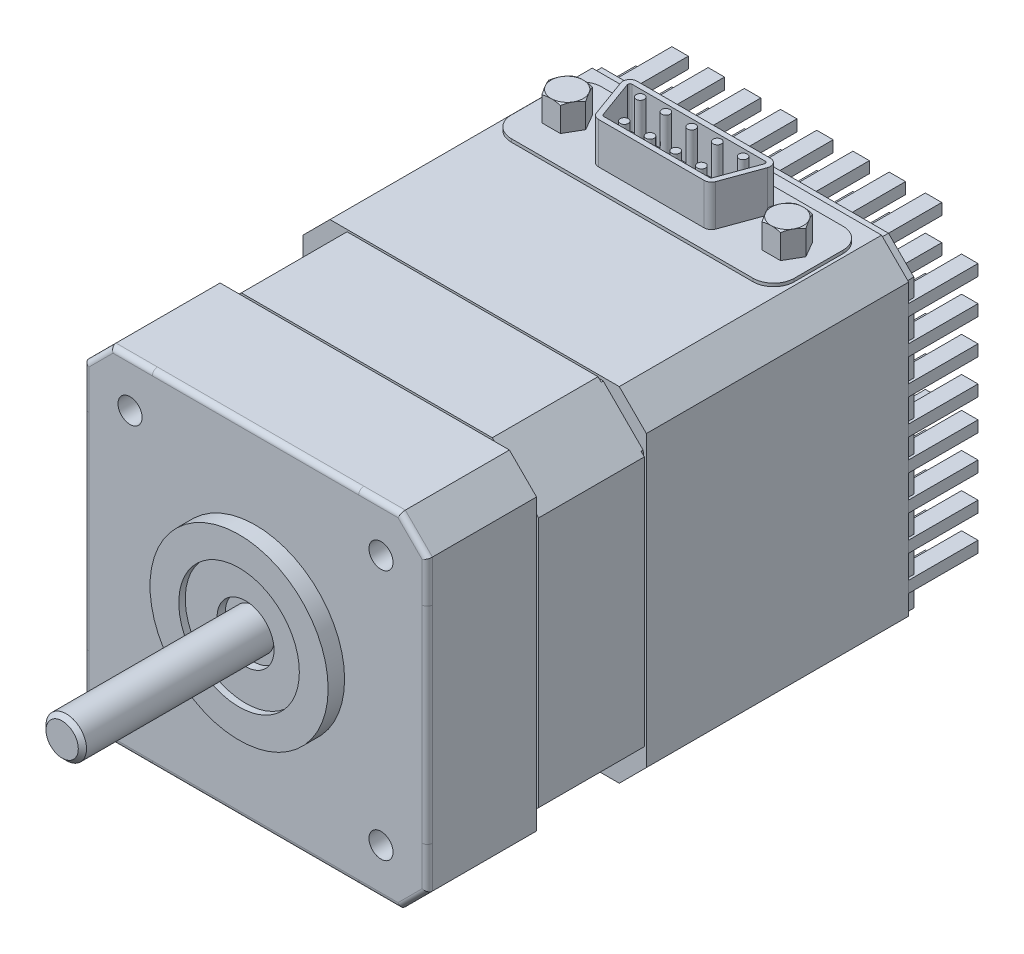
SolidWorks part; units mm, degrees
ref_plane "Front Plane" through (0, 0, 0) normal (0, 0, 1) x (1, 0, 0)
ref_plane "Top Plane" through (0, 0, 0) normal (0, 1, 0) x (1, 0, 0)
ref_plane "Right Plane" through (0, 0, 0) normal (1, 0, 0) x (0, 0, -1)
sketch "Sketch1" plane through (0, 0, 0) normal (0, 0, 1) x (1, 0, 0)
  line L0 (-21.209, -21.209) -> (21.209, 21.209) construction
  line L1 (-15.494, 21.209) -> (15.494, 21.209)
  line L2 (-21.209, 15.494) -> (-21.209, -15.494)
  line L3 (-15.494, -21.209) -> (15.494, -21.209)
  line L4 (21.209, 15.494) -> (21.209, -15.494)
  line L5 (0, 0) -> (0, 15.494) construction
  line L6 (-15.494, 15.494) -> (15.494, 15.494) construction
  line L7 (15.494, -15.494) -> (15.494, 15.494) construction
  line L8 (0, 0) -> (15.494, 0) construction
  circle A0 centre (-15.494, 15.494) radius 1.4859
  circle A1 centre (15.494, 15.494) radius 1.4859
  circle A2 centre (-15.494, -15.494) radius 1.4859
  circle A3 centre (15.494, -15.494) radius 1.4859
  arc A4 (15.494, 21.209) -> (21.209, 15.494) centre (15.494, 15.494) cw
  arc A5 (-15.494, 21.209) -> (-21.209, 15.494) centre (-15.494, 15.494) ccw
  arc A6 (-21.209, -15.494) -> (-15.494, -21.209) centre (-15.494, -15.494) ccw
  arc A7 (15.494, -21.209) -> (21.209, -15.494) centre (15.494, -15.494) ccw
  circle A8 centre (0, 0) radius 2.5019
  circle A9 centre (0, 0) radius 10.9982
  point P21 (-21.209, 21.209)
  dimension "H" = 2.9718
  dimension "A" = 5.0038
  dimension "Support Dia" = 21.9964
  dimension "E" = 42.418
  dimension "G" = 30.988
sketch "Sketch2" plane through (0, 0, 0) normal (0, 0, 1) x (1, 0, 0)
  line L0 (-15.494, 21.209) -> (15.494, 21.209) construction
  line L1 (21.209, 15.494) -> (21.209, -15.494) construction
  line L2 (-15.494, -21.209) -> (15.494, -21.209) construction
  line L3 (-21.209, 15.494) -> (-21.209, -15.494) construction
  line L4 (-15.494, 21.209) -> (15.494, 21.209)
  line L5 (21.209, 15.494) -> (21.209, -15.494)
  line L6 (-15.494, -21.209) -> (15.494, -21.209)
  line L7 (-21.209, 15.494) -> (-21.209, -15.494)
  arc A0 (21.209, 15.494) -> (15.494, 21.209) centre (15.494, 15.494) ccw construction
  arc A1 (15.494, -21.209) -> (21.209, -15.494) centre (15.494, -15.494) ccw construction
  arc A2 (-21.209, -15.494) -> (-15.494, -21.209) centre (-15.494, -15.494) ccw construction
  arc A3 (-15.494, 21.209) -> (-21.209, 15.494) centre (-15.494, 15.494) ccw construction
  arc A4 (21.209, 15.494) -> (15.494, 21.209) centre (15.494, 15.494) ccw
  arc A5 (15.494, -21.209) -> (21.209, -15.494) centre (15.494, -15.494) ccw
  arc A6 (-21.209, -15.494) -> (-15.494, -21.209) centre (-15.494, -15.494) ccw
  arc A7 (-15.494, 21.209) -> (-21.209, 15.494) centre (-15.494, 15.494) ccw
extrude "Extrude1" add sketch "Sketch2" against normal blind 68.072
ref_plane "Plane1" through (0, 0, -13.6144) normal (0, 0, 1) x (1, 0, 0)
ref_plane "Plane2" through (0, 0, -26.924) normal (0, 0, -1) x (-1, 0, 0)
sketch "Sketch3" plane through (0, 0, -13.6144) normal (0, 0, 1) x (1, 0, 0)
  line L4 (-21.209, 15.494) -> (-21.209, -15.494)
  line L5 (-15.494, -21.209) -> (15.494, -21.209)
  line L6 (21.209, -15.494) -> (21.209, 15.494)
  line L7 (15.494, 21.209) -> (-15.494, 21.209)
  line L8 (-21.209, 15.494) -> (-21.209, -15.494)
  line L9 (-15.494, -21.209) -> (15.494, -21.209)
  line L10 (21.209, -15.494) -> (21.209, 15.494)
  line L11 (15.494, 21.209) -> (-15.494, 21.209)
  arc A4 (-15.494, 21.209) -> (-21.209, 15.494) centre (-15.494, 15.494) ccw
  arc A5 (-21.209, -15.494) -> (-15.494, -21.209) centre (-15.494, -15.494) ccw
  arc A6 (15.494, -21.209) -> (21.209, -15.494) centre (15.494, -15.494) ccw
  arc A7 (21.209, 15.494) -> (15.494, 21.209) centre (15.494, 15.494) ccw
  arc A8 (-15.494, 21.209) -> (-21.209, 15.494) centre (-15.494, 15.494) ccw
  arc A9 (-21.209, -15.494) -> (-15.494, -21.209) centre (-15.494, -15.494) ccw
  arc A10 (15.494, -21.209) -> (21.209, -15.494) centre (15.494, -15.494) ccw
  arc A11 (21.209, 15.494) -> (15.494, 21.209) centre (15.494, 15.494) ccw
  dimension "D1" = 0
extrude "Cut-Extrude-Thin1" cut sketch "Sketch3" against normal mid plane 0.254 thin thin type mid plane wall 0.762
sketch "Sketch4" plane through (0, 0, -26.924) normal (0, 0, -1) x (-1, 0, 0)
  line L4 (21.209, -15.494) -> (21.209, 15.494)
  line L5 (-15.494, -21.209) -> (15.494, -21.209)
  line L6 (-21.209, 15.494) -> (-21.209, -15.494)
  line L7 (15.494, 21.209) -> (-15.494, 21.209)
  line L8 (21.209, -15.494) -> (21.209, 15.494)
  line L9 (-15.494, -21.209) -> (15.494, -21.209)
  line L10 (-21.209, 15.494) -> (-21.209, -15.494)
  line L11 (15.494, 21.209) -> (-15.494, 21.209)
  arc A4 (15.494, -21.209) -> (21.209, -15.494) centre (15.494, -15.494) ccw
  arc A5 (-21.209, -15.494) -> (-15.494, -21.209) centre (-15.494, -15.494) ccw
  arc A6 (-15.494, 21.209) -> (-21.209, 15.494) centre (-15.494, 15.494) ccw
  arc A7 (21.209, 15.494) -> (15.494, 21.209) centre (15.494, 15.494) ccw
  arc A8 (15.494, -21.209) -> (21.209, -15.494) centre (15.494, -15.494) ccw
  arc A9 (-21.209, -15.494) -> (-15.494, -21.209) centre (-15.494, -15.494) ccw
  arc A10 (-15.494, 21.209) -> (-21.209, 15.494) centre (-15.494, 15.494) ccw
  arc A11 (21.209, 15.494) -> (15.494, 21.209) centre (15.494, 15.494) ccw
  dimension "D1" = 0
extrude "Cut-Extrude-Thin2" cut sketch "Sketch4" against normal mid plane 0.254 thin thin type mid plane wall 0.762
sketch "Sketch5" plane through (0, 0, 0) normal (0, 0, 1) x (1, 0, 0)
  circle A0 centre (0, 0) radius 10.9982 construction
  circle A1 centre (0, 0) radius 10.9982
extrude "Extrude2" add sketch "Sketch5" along normal blind 2.032
sketch "Sketch6" plane through (0, 0, 0) normal (0, 0, 1) x (1, 0, 0)
  circle A0 centre (0, 0) radius 2.5019 construction
  circle A1 centre (0, 0) radius 2.5019
extrude "Extrude3" add sketch "Sketch6" along normal blind 23.876
chamfer "Chamfer1" distance 0.508 angle 45 1 edges at (2.5019, 0, 23.876)
sketch "Sketch7" plane through (0, 0, 0) normal (0, 0, 1) x (1, 0, 0)
  circle A0 centre (15.494, 15.494) radius 1.4859 construction
  circle A1 centre (15.494, -15.494) radius 1.4859 construction
  circle A2 centre (-15.494, -15.494) radius 1.4859 construction
  circle A3 centre (-15.494, 15.494) radius 1.4859 construction
  circle A4 centre (15.494, 15.494) radius 1.4859
  circle A5 centre (15.494, -15.494) radius 1.4859
  circle A6 centre (-15.494, -15.494) radius 1.4859
  circle A7 centre (-15.494, 15.494) radius 1.4859
extrude "Cut-Extrude1" cut sketch "Sketch7" against normal blind 3.9624
sketch "Sketch9" plane through (0, 0, 2.032) normal (0, 0, 1) x (1, 0, 0)
  circle A0 centre (0, 0) radius 2.5019 construction
  circle A1 centre (0, 0) radius 2.5019
  circle A4 centre (0, 0) radius 7.4422
  circle A5 centre (0, 0) radius 7.4422
  dimension "D1" = 3.556
extrude "Cut-Extrude3" cut sketch "Sketch9" against normal blind 0.8001
sketch "Sketch8" plane through (0, 0, 1.2319) normal (0, 0, 1) x (1, 0, 0)
  circle A0 centre (0, 0) radius 2.5019 construction
  circle A1 centre (0, 0) radius 2.5019
  circle A2 centre (0, 0) radius 3.5179
  dimension "D1" = 1.016
extrude "Cut-Extrude2" cut sketch "Sketch8" against normal blind 1.016
sketch "Sketch10" plane through (0, 0, -68.072) normal (0, 0, -1) x (-1, 0, 0)
  line L0 (9.779, 15.494) -> (9.779, 21.209)
  line L1 (15.494, 9.779) -> (21.209, 9.779)
  line L2 (-9.779, 15.494) -> (-9.779, 21.209)
  line L3 (-15.494, 9.779) -> (-21.209, 9.779)
  line L4 (-21.209, -9.779) -> (-15.494, -9.779)
  line L5 (-9.779, -15.494) -> (-9.779, -21.209)
  line L6 (9.779, -15.494) -> (9.779, -21.209)
  line L7 (15.494, -9.779) -> (21.209, -9.779)
  line L8 (-21.209, 15.494) -> (-21.209, -15.494) construction
  line L9 (-21.209, 21.209) -> (-9.779, 21.209)
  line L10 (-21.209, 21.209) -> (-21.209, 9.779)
  line L11 (-21.209, -21.209) -> (-9.779, -21.209)
  line L12 (21.209, 21.209) -> (21.209, 9.779)
  line L13 (15.494, -21.209) -> (-15.494, -21.209) construction
  line L14 (15.494, 21.209) -> (-15.494, 21.209) construction
  line L15 (21.209, 15.494) -> (21.209, -15.494) construction
  line L16 (21.209, -9.779) -> (21.209, -21.209)
  line L17 (9.779, 21.209) -> (21.209, 21.209)
  line L18 (-21.209, -9.779) -> (-21.209, -21.209)
  line L19 (9.779, -21.209) -> (21.209, -21.209)
  arc A0 (-15.494, 9.779) -> (-9.779, 15.494) centre (-15.494, 15.494) ccw
  arc A1 (9.779, 15.494) -> (15.494, 9.779) centre (15.494, 15.494) ccw
  arc A2 (15.494, -9.779) -> (9.779, -15.494) centre (15.494, -15.494) ccw
  arc A3 (-9.779, -15.494) -> (-15.494, -9.779) centre (-15.494, -15.494) ccw
  arc A4 (-21.209, -15.494) -> (-15.494, -21.209) centre (-15.494, -15.494) ccw construction
  circle A5 centre (-15.494, 15.494) radius 1.4859 construction
  circle A6 centre (15.494, 15.494) radius 1.4859 construction
  circle A7 centre (15.494, -15.494) radius 1.4859 construction
extrude "Cut-Extrude4" cut sketch "Sketch10" against normal blind 7.9375
fillet "Fillet1" radius 1.016 8 edges at (-21.209, -9.779, -64.1033) (-9.779, -21.209, -64.1033) (21.209, -9.779, -64.1033) (9.779, -21.209, -64.1033) (-21.209, 9.779, -64.1033) (-9.779, 21.209, -64.1033) (9.779, 21.209, -64.1033) (21.209, 9.779, -64.1033)
fillet "Fillet2" radius 0.635 44 edges at (-21.209, -12.1285, -60.1345) (-19.5351, -19.5351, -60.1345) (12.1285, -21.209, -60.1345) (21.209, -12.1285, -60.1345) (12.1285, 21.209, -60.1345) (19.5351, 19.5351, -60.1345) (19.5351, 19.5351, 0) (21.209, 0, 0) (19.5351, -19.5351, 0) (0, -21.209, 0) (-19.5351, -19.5351, 0) (-21.209, 0, 0) (-19.5351, 19.5351, 0) (-12.1285, 21.209, -60.1345) (-21.209, 12.1285, -60.1345) (-9.779, 17.8435, -68.072) (-11.4529, 11.4529, -68.072) (-17.8435, 9.779, -68.072) (-20.9114, 9.4814, -68.072) (-21.209, 0, -68.072) (-20.9114, -9.4814, -68.072) (-17.8435, -9.779, -68.072) (-11.4529, -11.4529, -68.072) (-9.779, -17.8435, -68.072) (-9.4814, -20.9114, -68.072) (0, -21.209, -68.072) (9.4814, -20.9114, -68.072) (9.779, -17.8435, -68.072) (11.4529, -11.4529, -68.072) (17.8435, -9.779, -68.072) (20.9114, -9.4814, -68.072) (21.209, 0, -68.072) (20.9114, 9.4814, -68.072) (17.8435, 9.779, -68.072) (11.4529, 11.4529, -68.072) (9.779, 17.8435, -68.072) (9.4814, 20.9114, -68.072) (0, 21.209, -68.072) (-12.1285, -21.209, -60.1345) (19.5351, -19.5351, -60.1345) (21.209, 12.1285, -60.1345) (0, 21.209, 0) (-19.5351, 19.5351, -60.1345) (-9.4814, 20.9114, -68.072)
sketch "Sketch11" plane through (0, 0, -60.1345) normal (0, 0, -1) x (-1, 0, 0)
  circle A0 centre (15.494, 15.494) radius 1.4859 construction
  circle A1 centre (-15.494, 15.494) radius 5.08
  arc A2 (20.574, 15.494) -> (15.494, 20.574) centre (15.494, 15.494) ccw construction
  circle A3 centre (15.494, 15.494) radius 5.08
  circle A4 centre (15.494, -15.494) radius 5.08
  circle A5 centre (-15.494, -15.494) radius 5.08
  circle A6 centre (-15.494, 15.494) radius 1.4859 construction
  circle A7 centre (-15.494, -15.494) radius 1.4859 construction
  circle A8 centre (15.494, -15.494) radius 1.4859 construction
  arc A10 (12.0703, 11.7415) -> (12.0472, 11.7644) centre (12.6853, 12.3834) ccw construction
extrude "Extrude4" add sketch "Sketch11" along normal blind 0.508
dome "Dome1" faces to dome 1 distance 3.9688 reverse direction no elliptical dome yes face at (10.414, -15.494, -60.6425) parameters "D1"=3.9688
dome "Dome2" faces to dome 1 distance 3.9688 reverse direction no elliptical dome yes face at (-20.574, -15.494, -60.6425) parameters "D1"=3.9688
dome "Dome3" faces to dome 1 distance 3.9688 reverse direction no elliptical dome yes face at (10.414, 15.494, -60.6425) parameters "D1"=3.9688
dome "Dome4" faces to dome 1 distance 3.9688 reverse direction no elliptical dome yes face at (-20.574, 15.494, -60.6425) parameters "D1"=3.9688
sketch "Sketch12" [suppressed] plane through (0, 14.097, 0) normal (0, 1, 0) x (-1, 0, 0)
  line L0 (0, 0) -> (0, -22.987) construction
  line L1 (-8.001, -32.004) -> (8.001, -32.004)
  line L2 (-8.001, -32.004) -> (-8.001, -22.987)
  line L3 (-8.001, -22.987) -> (8.001, -22.987)
  line L4 (8.001, -32.004) -> (8.001, -22.987)
  line L5 (8.001, -32.004) -> (-8.001, -32.004) construction
  line L6 (-8.001, -29.083) -> (-8.001, -31.369) construction
  line L7 (-11.557, -22.987) -> (11.557, -22.987) construction
extrude "Extrude5" [suppressed] add sketch "Sketch12" along normal blind 2.3749 and the other way up to next
chamfer "Chamfer2" [suppressed] distance 2.286 distance2 0.762
fillet "Fillet3" [suppressed] radius 0.508
sketch "Sketch13" [suppressed] plane through (0, 0, -32.004) normal (0, 0, -1) x (-1, 0, 0)
  line L1 (-7.493, 13.589) -> (7.493, 13.589)
  line L7 (-7.493, 16.4719) -> (7.493, 16.4719) construction
  line L8 (8.001, 13.462) -> (8.001, 15.9639) construction
  line L9 (-8.001, 13.462) -> (-8.001, 15.9639) construction
  line L13 (7.493, 15.9639) -> (7.493, 13.589)
  line L14 (-7.493, 15.9639) -> (7.493, 15.9639)
  line L15 (-7.493, 13.589) -> (-7.493, 15.9639)
  dimension "D1" = 0.508
  dimension "D2" = 0.508
  dimension "D3" = 0.508
  dimension "D4" = 2.3749
extrude "Cut-Extrude5" [suppressed] cut sketch "Sketch13" against normal blind 3.175
fillet "Fillet4" [suppressed] radius 0.254
sketch "Sketch14" [suppressed] plane through (0, 0, -28.829) normal (0, 0, -1) x (-1, 0, 0)
  line L4 (7.493, 13.589) -> (7.493, 15.9639)
  line L5 (7.493, 15.9639) -> (-7.493, 15.9639)
  line L6 (-7.493, 15.9639) -> (-7.493, 13.589)
  line L7 (-7.493, 13.589) -> (7.493, 13.589)
  line L8 (7.493, 13.589) -> (7.493, 15.9639)
  line L9 (7.493, 15.9639) -> (-7.493, 15.9639)
  line L10 (-7.493, 15.9639) -> (-7.493, 13.589)
  line L11 (-7.493, 13.589) -> (7.493, 13.589)
  dimension "D1" = 0
extrude "Extrude6" [suppressed] add sketch "Sketch14" along normal blind 3.9624
sketch "Sketch15" [suppressed] plane through (0, 0, -32.7914) normal (0, 0, -1) x (-1, 0, 0)
  line L8 (-7.874, 13.208) -> (7.874, 13.208)
  line L9 (7.874, 13.208) -> (7.874, 16.3449)
  line L10 (7.874, 16.3449) -> (-7.874, 16.3449)
  line L11 (-7.874, 16.3449) -> (-7.874, 13.208)
  line L12 (-7.874, 13.208) -> (7.874, 13.208)
  line L13 (7.874, 13.208) -> (7.874, 16.3449)
  line L14 (7.874, 16.3449) -> (-7.874, 16.3449)
  line L15 (-7.874, 16.3449) -> (-7.874, 13.208)
  dimension "D1" = 0.381
extrude "Extrude7" [suppressed] add sketch "Sketch15" along normal blind 0.381
fillet "Fillet5" [suppressed] radius 0.762
sketch "Sketch16" [suppressed] plane through (0, 17.653, 0) normal (0, 1, 0) x (-1, 0, 0)
  line L0 (12.954, -14.7139) -> (-12.954, -14.7139) construction
  line L1 (-6.477, -14.7139) -> (6.477, -14.7139)
  line L2 (-6.477, -14.7139) -> (-6.477, -19.4764)
  line L3 (-6.477, -19.4764) -> (6.477, -19.4764)
  line L4 (6.477, -14.7139) -> (6.477, -19.4764)
  line L5 (7.239, -33.401) -> (7.239, -31.877) construction
  point P6 (7.239, -32.639)
  dimension "D1" = 0.762
  dimension "D2" = 0.762
  dimension "D3" = 4.7625
extrude "Extrude8" [suppressed] add sketch "Sketch16" along normal blind 1.397
fillet "Fillet6" [suppressed] radius 0.889
sketch "Sketch17" [suppressed] plane through (0, 19.05, 0) normal (0, 1, 0) x (-1, 0, 0)
  line L8 (5.588, -15.2219) -> (-5.588, -15.2219)
  line L9 (-5.969, -15.6029) -> (-5.969, -18.5874)
  line L10 (-5.588, -18.9684) -> (5.588, -18.9684)
  line L11 (5.969, -18.5874) -> (5.969, -15.6029)
  line L12 (5.588, -15.2219) -> (-5.588, -15.2219)
  line L13 (-5.969, -15.6029) -> (-5.969, -18.5874)
  line L14 (-5.588, -18.9684) -> (5.588, -18.9684)
  line L15 (5.969, -18.5874) -> (5.969, -15.6029)
  arc A8 (-5.588, -15.2219) -> (-5.969, -15.6029) centre (-5.588, -15.6029) ccw
  arc A9 (-5.969, -18.5874) -> (-5.588, -18.9684) centre (-5.588, -18.5874) ccw
  arc A10 (5.588, -18.9684) -> (5.969, -18.5874) centre (5.588, -18.5874) ccw
  arc A11 (5.969, -15.6029) -> (5.588, -15.2219) centre (5.588, -15.6029) ccw
  arc A12 (-5.588, -15.2219) -> (-5.969, -15.6029) centre (-5.588, -15.6029) ccw
  arc A13 (-5.969, -18.5874) -> (-5.588, -18.9684) centre (-5.588, -18.5874) ccw
  arc A14 (5.588, -18.9684) -> (5.969, -18.5874) centre (5.588, -18.5874) ccw
  arc A15 (5.969, -15.6029) -> (5.588, -15.2219) centre (5.588, -15.6029) ccw
  dimension "D1" = 0.508
extrude "Cut-Extrude6" [suppressed] cut sketch "Sketch17" against normal blind 0.127
sketch "Sketch18" plane through (0, 0, 0) normal (0, 0, 1) x (1, 0, 0)
  line L0 (-21.209, 17.8612) -> (-17.8612, 21.209)
  line L1 (0, 0) -> (0, 16.0858) construction
  line L2 (-15.494, 21.209) -> (15.494, 21.209) construction
  line L3 (-21.209, -15.494) -> (-21.209, 15.494) construction
  line L4 (-17.8612, 21.209) -> (-12.7381, 21.209)
  line L5 (-21.209, 12.7381) -> (-21.209, 17.8612)
  line L6 (-21.209, 12.7381) -> (-15.494, 12.7381)
  line L7 (-12.7381, 15.494) -> (-12.7381, 21.209)
  line L8 (12.7381, 15.494) -> (12.7381, 21.209)
  line L9 (21.209, 12.7381) -> (15.494, 12.7381)
  line L10 (21.209, 12.7381) -> (21.209, 17.8612)
  line L11 (17.8612, 21.209) -> (12.7381, 21.209)
  line L12 (21.209, 17.8612) -> (17.8612, 21.209)
  line L13 (0, 0) -> (14.0244, 0) construction
  line L14 (21.209, -17.8612) -> (17.8612, -21.209)
  line L15 (17.8612, -21.209) -> (12.7381, -21.209)
  line L16 (21.209, -12.7381) -> (21.209, -17.8612)
  line L17 (21.209, -12.7381) -> (15.494, -12.7381)
  line L18 (12.7381, -15.494) -> (12.7381, -21.209)
  line L19 (-12.7381, -15.494) -> (-12.7381, -21.209)
  line L20 (-21.209, -12.7381) -> (-15.494, -12.7381)
  line L21 (-21.209, -12.7381) -> (-21.209, -17.8612)
  line L22 (-17.8612, -21.209) -> (-12.7381, -21.209)
  line L23 (-21.209, -17.8612) -> (-17.8612, -21.209)
  arc A0 (12.7381, 15.494) -> (15.494, 12.7381) centre (15.494, 15.494) cw
  arc A1 (-15.494, 21.209) -> (-21.209, 15.494) centre (-15.494, 15.494) ccw construction
  arc A2 (-12.7381, -15.494) -> (-15.494, -12.7381) centre (-15.494, -15.494) cw
  arc A3 (12.7381, -15.494) -> (15.494, -12.7381) centre (15.494, -15.494) ccw
  circle A4 centre (-15.494, 15.494) radius 2.7559
  arc A5 (-12.7381, 15.494) -> (-15.494, 12.7381) centre (-15.494, 15.494) ccw
  dimension "D1" = 45
  dimension "D2" = 1.27
extrude "Extrude9" add sketch "Sketch18" against normal up to surface (13.4874 mm away) up to face at (0, 0, -13.4874)
fillet "Fillet7" radius 0.635 12 edges at (-21.209, -15.2997, 0) (-19.5351, -19.5351, 0) (-15.2997, -21.209, 0) (15.2997, -21.209, 0) (19.5351, -19.5351, 0) (21.209, -15.2997, 0) (21.209, 15.2997, 0) (19.5351, 19.5351, 0) (15.2997, 21.209, 0) (-15.2997, 21.209, 0) (-19.5351, 19.5351, 0) (-21.209, 15.2997, 0)
sketch "Sketch19" plane through (0, 0, -27.051) normal (0, 0, 1) x (1, 0, 0)
  line L5 (12.7381, 21.209) -> (12.7381, 15.494)
  line L6 (15.494, 12.7381) -> (21.209, 12.7381)
  line L7 (21.209, 12.7381) -> (21.209, 17.8612)
  line L8 (21.209, 17.8612) -> (17.8612, 21.209)
  line L9 (17.8612, 21.209) -> (12.7381, 21.209)
  line L10 (12.7381, 21.209) -> (12.7381, 15.494)
  line L11 (15.494, 12.7381) -> (21.209, 12.7381)
  line L12 (21.209, 12.7381) -> (21.209, 17.8612)
  line L13 (21.209, 17.8612) -> (17.8612, 21.209)
  line L14 (17.8612, 21.209) -> (12.7381, 21.209)
  line L15 (-21.209, 12.7381) -> (-15.494, 12.7381)
  line L16 (-21.209, 17.8612) -> (-21.209, 12.7381)
  line L17 (-17.8612, 21.209) -> (-21.209, 17.8612)
  line L18 (-12.7381, 21.209) -> (-17.8612, 21.209)
  line L19 (-12.7381, 15.494) -> (-12.7381, 21.209)
  line L20 (-21.209, 12.7381) -> (-15.494, 12.7381)
  line L21 (-21.209, 17.8612) -> (-21.209, 12.7381)
  line L22 (-17.8612, 21.209) -> (-21.209, 17.8612)
  line L23 (-12.7381, 21.209) -> (-17.8612, 21.209)
  line L24 (-12.7381, 15.494) -> (-12.7381, 21.209)
  line L25 (-12.7381, -21.209) -> (-12.7381, -15.494)
  line L26 (-15.494, -12.7381) -> (-21.209, -12.7381)
  line L27 (-21.209, -12.7381) -> (-21.209, -17.8612)
  line L28 (-21.209, -17.8612) -> (-17.8612, -21.209)
  line L29 (-17.8612, -21.209) -> (-12.7381, -21.209)
  line L30 (-12.7381, -21.209) -> (-12.7381, -15.494)
  line L31 (-15.494, -12.7381) -> (-21.209, -12.7381)
  line L32 (-21.209, -12.7381) -> (-21.209, -17.8612)
  line L33 (-21.209, -17.8612) -> (-17.8612, -21.209)
  line L34 (-17.8612, -21.209) -> (-12.7381, -21.209)
  line L35 (17.8612, -21.209) -> (21.209, -17.8612)
  line L36 (12.7381, -21.209) -> (17.8612, -21.209)
  line L37 (12.7381, -15.494) -> (12.7381, -21.209)
  line L38 (21.209, -12.7381) -> (15.494, -12.7381)
  line L39 (21.209, -17.8612) -> (21.209, -12.7381)
  line L40 (17.8612, -21.209) -> (21.209, -17.8612)
  line L41 (12.7381, -21.209) -> (17.8612, -21.209)
  line L42 (12.7381, -15.494) -> (12.7381, -21.209)
  line L43 (21.209, -12.7381) -> (15.494, -12.7381)
  line L44 (21.209, -17.8612) -> (21.209, -12.7381)
  arc A1 (15.494, 12.7381) -> (12.7381, 15.494) centre (15.494, 15.494) ccw
  arc A2 (15.494, 12.7381) -> (12.7381, 15.494) centre (15.494, 15.494) ccw
  arc A3 (-12.7381, 15.494) -> (-15.494, 12.7381) centre (-15.494, 15.494) ccw
  arc A4 (-12.7381, 15.494) -> (-15.494, 12.7381) centre (-15.494, 15.494) ccw
  arc A5 (-15.494, -12.7381) -> (-12.7381, -15.494) centre (-15.494, -15.494) ccw
  arc A6 (-15.494, -12.7381) -> (-12.7381, -15.494) centre (-15.494, -15.494) ccw
  arc A7 (12.7381, -15.494) -> (15.494, -12.7381) centre (15.494, -15.494) ccw
  arc A8 (12.7381, -15.494) -> (15.494, -12.7381) centre (15.494, -15.494) ccw
  dimension "D1" = 0
  dimension "D2" = 0
  dimension "D3" = 0
  dimension "D4" = 0
extrude "Extrude10" add sketch "Sketch19" against normal up to surface (33.0835 mm away) up to face at (14.2873, 14.2873, -60.1345)
sketch "Sketch21" plane through (0, 21.209, 0) normal (0, 1, 0) x (-1, 0, 0)
  line L0 (-17.4625, -52.07) -> (0, -52.07) construction
  line L1 (-17.4625, -57.6263) -> (17.4625, -57.6262)
  line L2 (-17.4625, -57.6263) -> (-17.4625, -46.5138)
  line L3 (-17.4625, -46.5138) -> (17.4625, -46.5138)
  line L4 (17.4625, -57.6262) -> (17.4625, -46.5138)
  line L5 (8.763, -68.072) -> (-8.763, -68.072) construction
  line L6 (0, 0) -> (0, -52.07) construction
  line L7 (-13.589, -61.8191) -> (-13.589, -41.9159) construction
  line L8 (-21.209, -60.1345) -> (-21.209, -27.051) construction
  line L9 (6.35, -53.848) -> (-6.2857, -53.848) construction
  line L10 (0, -52.07) -> (0, -57.6262) construction
  line L11 (14.7328, -54.0512) -> (12.4452, -54.0512)
  line L12 (-11.3013, -52.07) -> (-12.4452, -50.0888)
  line L13 (-12.4452, -50.0888) -> (-14.7328, -50.0888)
  line L14 (-14.7328, -50.0888) -> (-15.8767, -52.07)
  line L15 (-15.8767, -52.07) -> (-14.7328, -54.0512)
  line L16 (-14.7328, -54.0512) -> (-12.4452, -54.0512)
  line L17 (-12.4452, -54.0512) -> (-11.3013, -52.07)
  line L18 (15.8767, -52.07) -> (14.7328, -54.0512)
  line L19 (14.7328, -50.0888) -> (15.8767, -52.07)
  line L20 (12.4452, -50.0888) -> (14.7328, -50.0888)
  line L21 (11.3013, -52.07) -> (12.4452, -50.0888)
  line L22 (12.4452, -54.0512) -> (11.3013, -52.07)
  line L23 (-9.4966, -55.3402) -> (9.4966, -55.3402)
  line L24 (9.4966, -55.3402) -> (7.1438, -48.876)
  line L25 (7.1438, -48.876) -> (-7.1437, -48.876)
  line L26 (-7.1437, -48.876) -> (-9.4966, -55.3402)
  line L27 (6.3103, -50.292) -> (-6.2857, -50.292) construction
  line L28 (-6.2857, -50.292) -> (-6.2857, -52.07) construction
  line L29 (-6.2857, -53.848) -> (-6.2857, -52.07) construction
  circle A0 centre (-13.589, -52.07) radius 1.9812 construction
  circle A1 centre (0, -53.848) radius 0.508
  circle A2 centre (1.5875, -50.292) radius 0.508
  circle A3 centre (4.7625, -50.292) radius 0.508
  circle A4 centre (6.35, -53.848) radius 0.508
  circle A5 centre (3.175, -53.848) radius 0.508
  circle A6 centre (-3.175, -53.848) radius 0.508
  circle A7 centre (-6.35, -53.848) radius 0.508
  circle A8 centre (-4.7625, -50.292) radius 0.508
  circle A9 centre (-1.5875, -50.292) radius 0.508
  dimension "D4" = 3.9624
  dimension "D13" = 1.016
  dimension "D1" = 16.002
  dimension "D2" = 7.62
  dimension "D3" = 2.286
  dimension "D5" = 17.4625
  dimension "D6" = 11.1125
  dimension "D7" = 2.3622
  dimension "D8" = 20
  dimension "D9" = 14.2875
  dimension "D10" = 7.1437
  dimension "D11" = 1.778
  dimension "D12" = 1.5875
  dimension "D14" = 3.175
  dimension "D15" = 3.175
  dimension "D16" = 3.175
sketch "Sketch22" plane through (0, 0, -13.7414) normal (0, 0, 1) x (1, 0, 0)
  line L0 (15.494, 21.209) -> (21.209, 15.494)
  line L1 (21.209, 15.494) -> (21.209, 21.209)
  line L2 (21.209, 21.209) -> (15.494, 21.209)
  line L3 (0, 0) -> (0, 24.2976) construction
  line L4 (-21.209, 21.209) -> (-15.494, 21.209)
  line L5 (-21.209, 15.494) -> (-21.209, 21.209)
  line L6 (-15.494, 21.209) -> (-21.209, 15.494)
  line L7 (0, 0) -> (18.2844, 0) construction
  line L8 (-15.494, -21.209) -> (-21.209, -15.494)
  line L9 (-21.209, -15.494) -> (-21.209, -21.209)
  line L10 (-21.209, -21.209) -> (-15.494, -21.209)
  line L11 (21.209, -21.209) -> (15.494, -21.209)
  line L12 (21.209, -15.494) -> (21.209, -21.209)
  line L13 (15.494, -21.209) -> (21.209, -15.494)
extrude "Cut-Extrude7" cut sketch "Sketch22" against normal up to surface (13.3096 mm away) up to face at (0, 0, -27.051)
sketch "Sketch23" plane through (0, 0, -68.072) normal (0, 0, -1) x (-1, 0, 0)
  circle A0 centre (-15.494, 15.494) radius 5.08 construction
  circle A1 centre (-15.494, 15.494) radius 5.08
  circle A2 centre (15.494, 15.494) radius 5.08 construction
  circle A3 centre (15.494, 15.494) radius 5.08
  circle A4 centre (15.494, -15.494) radius 5.08 construction
  circle A5 centre (15.494, -15.494) radius 5.08
  circle A6 centre (-15.494, -15.494) radius 5.08 construction
  circle A7 centre (-15.494, -15.494) radius 5.08
extrude "Cut-Extrude8" cut sketch "Sketch23" against normal up to surface (7.9375 mm away) up to face at (10.414, 15.494, -60.1345)
sketch "Sketch30" plane through (0, 0, -60.1345) normal (0, 0, -1) x (-1, 0, 0)
  line L0 (21.209, 17.8612) -> (21.209, 12.7381) construction
  line L1 (21.209, 17.8612) -> (21.209, 12.7381)
  line L2 (-17.4625, 21.209) -> (17.4625, 21.209) construction
  line L3 (-17.8612, 21.209) -> (17.8612, 21.209)
  line L4 (-21.209, 15.494) -> (-21.209, -15.494) construction
  line L5 (-21.209, 17.8612) -> (-21.209, -17.8612)
  line L6 (15.494, -21.209) -> (-15.494, -21.209) construction
  line L7 (17.8612, -21.209) -> (-17.8612, -21.209)
  line L8 (21.209, -17.8612) -> (17.8612, -21.209) construction
  line L9 (-17.8612, -21.209) -> (-21.209, -17.8612) construction
  line L10 (21.209, -17.8612) -> (17.8612, -21.209)
  line L11 (-17.8612, -21.209) -> (-21.209, -17.8612)
  line L12 (-21.209, 17.8612) -> (-17.8612, 21.209) construction
  line L13 (17.8612, 21.209) -> (21.209, 17.8612) construction
  line L14 (-21.209, 17.8612) -> (-17.8612, 21.209)
  line L15 (17.8612, 21.209) -> (21.209, 17.8612)
sketch "Sketch31" plane through (0, 0, -60.1345) normal (0, 0, -1) x (-1, 0, 0)
  line L0 (21.209, 15.494) -> (21.209, -15.494) construction
  line L1 (-21.209, 21.209) -> (21.209, 21.209)
  line L2 (-21.209, 21.209) -> (-21.209, -21.209)
  line L3 (-21.209, -21.209) -> (21.209, -21.209)
  line L4 (21.209, 21.209) -> (21.209, -21.209)
  line L5 (-21.209, 15.494) -> (-21.209, -15.494) construction
  line L6 (15.494, 21.209) -> (-15.494, 21.209) construction
  line L7 (15.494, -21.209) -> (-15.494, -21.209) construction
extrude "Extrude14" add sketch "Sketch31" along normal through all and the other way blind 0.635
sketch "Sketch32" plane through (0, 0, -68.072) normal (0, 0, -1) x (-1, 0, 0)
  line L4 (-21.209, 21.209) -> (-21.209, -21.209)
  line L5 (-21.209, -21.209) -> (21.209, -21.209)
  line L6 (21.209, -21.209) -> (21.209, 21.209)
  line L7 (21.209, 21.209) -> (-21.209, 21.209)
  line L8 (-21.209, 21.209) -> (-21.209, -21.209)
  line L9 (-21.209, -21.209) -> (21.209, -21.209)
  line L10 (21.209, -21.209) -> (21.209, 21.209)
  line L11 (21.209, 21.209) -> (-21.209, 21.209)
  dimension "D1" = 0
extrude "Cut-Extrude12" cut sketch "Sketch32" against normal blind 7.62
sketch "Sketch33" plane through (0, 0, -60.452) normal (0, 0, -1) x (-1, 0, 0)
  line L4 (21.209, 21.209) -> (-21.209, 21.209)
  line L5 (-21.209, 21.209) -> (-21.209, -21.209)
  line L6 (-21.209, -21.209) -> (21.209, -21.209)
  line L7 (21.209, -21.209) -> (21.209, 21.209)
  line L8 (21.209, 21.209) -> (-21.209, 21.209)
  line L9 (-21.209, 21.209) -> (-21.209, -21.209)
  line L10 (-21.209, -21.209) -> (21.209, -21.209)
  line L11 (21.209, -21.209) -> (21.209, 21.209)
  line L14 (-20.9396, 17.5918) -> (-17.5918, 20.9396)
  line L15 (-20.828, 17.7034) -> (-17.7034, 20.828)
  line L16 (20.828, 20.828) -> (-20.828, 20.828)
  line L17 (-20.828, 20.828) -> (-20.828, -20.828)
  line L18 (-20.828, -20.828) -> (20.828, -20.828)
  line L19 (20.828, -20.828) -> (20.828, 20.828)
  line L20 (17.7034, 20.828) -> (-17.7034, 20.828)
  line L21 (-20.828, 17.7034) -> (-20.828, -17.7034)
  line L22 (-17.7034, -20.828) -> (17.7034, -20.828)
  line L23 (20.828, -17.7034) -> (20.828, 17.7034)
  line L25 (17.5918, 20.9396) -> (20.9396, 17.5918)
  line L26 (17.7034, 20.828) -> (20.828, 17.7034)
  line L28 (-17.5918, -20.9396) -> (-20.9396, -17.5918)
  line L29 (-17.7034, -20.828) -> (-20.828, -17.7034)
  line L31 (20.9396, -17.5918) -> (17.5918, -20.9396)
  line L32 (20.828, -17.7034) -> (17.7034, -20.828)
  dimension "D1" = 0
  dimension "D2" = 0.381
  dimension "D3" = 0.381
  dimension "D4" = 0.381
  dimension "D5" = 0.381
  dimension "D6" = 0.381
extrude "Cut-Extrude13" cut sketch "Sketch33" against normal blind 1.016
sketch "Sketch34" plane through (0, 0, -60.452) normal (0, 0, -1) x (-1, 0, 0)
  line L1 (-3.2512, 2.6162) -> (-1.2192, 2.6162)
  line L2 (-3.2512, 2.6162) -> (-3.2512, 1.2192)
  line L3 (-3.2512, 1.2192) -> (-1.2192, 1.2192)
  line L4 (-1.2192, 2.6162) -> (-1.2192, 1.2192)
  line L5 (-2.2352, 1.2192) -> (-2.2352, 11.8055) construction
  line L6 (-7.7216, 2.6162) -> (-5.6896, 2.6162)
  line L7 (-7.7216, 2.6162) -> (-7.7216, 1.2192)
  line L8 (-7.7216, 1.2192) -> (-5.6896, 1.2192)
  line L9 (-5.6896, 2.6162) -> (-5.6896, 1.2192)
  line L10 (-12.192, 2.6162) -> (-10.16, 2.6162)
  line L11 (-12.192, 2.6162) -> (-12.192, 1.2192)
  line L12 (-12.192, 1.2192) -> (-10.16, 1.2192)
  line L13 (-10.16, 2.6162) -> (-10.16, 1.2192)
  line L14 (-16.6624, 2.6162) -> (-14.6304, 2.6162)
  line L15 (-16.6624, 2.6162) -> (-16.6624, 1.2192)
  line L16 (-16.6624, 1.2192) -> (-14.6304, 1.2192)
  line L17 (-14.6304, 2.6162) -> (-14.6304, 1.2192)
  line L18 (-21.1328, 2.6162) -> (-19.1008, 2.6162)
  line L19 (-21.1328, 2.6162) -> (-21.1328, 1.2192)
  line L20 (-21.1328, 1.2192) -> (-19.1008, 1.2192)
  line L21 (-19.1008, 2.6162) -> (-19.1008, 1.2192)
  line L22 (-3.2512, 2.6162) -> (-7.7216, 2.6162) construction
  line L23 (0, 0) -> (0, -5.8284) construction
  line L24 (19.1008, 2.6162) -> (19.1008, 1.2192)
  line L25 (21.1328, 1.2192) -> (19.1008, 1.2192)
  line L26 (21.1328, 2.6162) -> (21.1328, 1.2192)
  line L27 (21.1328, 2.6162) -> (19.1008, 2.6162)
  line L28 (14.6304, 2.6162) -> (14.6304, 1.2192)
  line L29 (16.6624, 1.2192) -> (14.6304, 1.2192)
  line L30 (16.6624, 2.6162) -> (16.6624, 1.2192)
  line L31 (16.6624, 2.6162) -> (14.6304, 2.6162)
  line L32 (10.16, 2.6162) -> (10.16, 1.2192)
  line L33 (12.192, 1.2192) -> (10.16, 1.2192)
  line L34 (12.192, 2.6162) -> (12.192, 1.2192)
  line L35 (12.192, 2.6162) -> (10.16, 2.6162)
  line L36 (5.6896, 2.6162) -> (5.6896, 1.2192)
  line L37 (7.7216, 1.2192) -> (5.6896, 1.2192)
  line L38 (7.7216, 2.6162) -> (7.7216, 1.2192)
  line L39 (7.7216, 2.6162) -> (5.6896, 2.6162)
  line L40 (3.2512, 2.6162) -> (1.2192, 2.6162)
  line L41 (1.2192, 2.6162) -> (1.2192, 1.2192)
  line L42 (3.2512, 1.2192) -> (1.2192, 1.2192)
  line L43 (3.2512, 2.6162) -> (3.2512, 1.2192)
  dimension "D1" = 2.032
  dimension "D2" = 1.397
  dimension "D3" = 1.2192
  dimension "D4" = 4.4704
  dimension "D5" = 1.2192
extrude "Extrude15" add sketch "Sketch34" along normal blind 7.62 and the other way blind 1.016
pattern_linear "LPattern2" count 5 spacing 4.2926 along (0, 1, 0) of "Extrude15"
mirror "Mirror1" about plane through (0, 0, 0) normal (0, 1, 0) of "Extrude15", "LPattern2"
sketch "Sketch35" plane through (0, 0, -60.452) normal (0, 0, -1) x (-1, 0, 0)
  line L4 (21.1328, 19.7866) -> (19.1008, 19.7866)
  line L5 (19.1008, 19.7866) -> (19.1008, 18.3896)
  line L6 (19.1008, 18.3896) -> (21.1328, 18.3896)
  line L7 (21.1328, 18.3896) -> (21.1328, 19.7866)
  line L8 (21.1328, 19.7866) -> (19.1008, 19.7866)
  line L9 (19.1008, 19.7866) -> (19.1008, 18.3896)
  line L10 (19.1008, 18.3896) -> (21.1328, 18.3896)
  line L11 (21.1328, 18.3896) -> (21.1328, 19.7866)
  line L12 (19.1008, -19.7866) -> (21.1328, -19.7866)
  line L13 (21.1328, -19.7866) -> (21.1328, -18.3896)
  line L14 (21.1328, -18.3896) -> (19.1008, -18.3896)
  line L15 (19.1008, -18.3896) -> (19.1008, -19.7866)
  line L16 (19.1008, -19.7866) -> (21.1328, -19.7866)
  line L17 (21.1328, -19.7866) -> (21.1328, -18.3896)
  line L18 (21.1328, -18.3896) -> (19.1008, -18.3896)
  line L19 (19.1008, -18.3896) -> (19.1008, -19.7866)
  line L20 (-21.1328, 19.7866) -> (-21.1328, 18.3896)
  line L21 (-21.1328, 18.3896) -> (-19.1008, 18.3896)
  line L22 (-19.1008, 18.3896) -> (-19.1008, 19.7866)
  line L23 (-19.1008, 19.7866) -> (-21.1328, 19.7866)
  line L24 (-21.1328, 19.7866) -> (-21.1328, 18.3896)
  line L25 (-21.1328, 18.3896) -> (-19.1008, 18.3896)
  line L26 (-19.1008, 18.3896) -> (-19.1008, 19.7866)
  line L27 (-19.1008, 19.7866) -> (-21.1328, 19.7866)
  line L28 (-21.1328, -18.3896) -> (-21.1328, -19.7866)
  line L29 (-21.1328, -19.7866) -> (-19.1008, -19.7866)
  line L30 (-19.1008, -19.7866) -> (-19.1008, -18.3896)
  line L31 (-19.1008, -18.3896) -> (-21.1328, -18.3896)
  line L32 (-21.1328, -18.3896) -> (-21.1328, -19.7866)
  line L33 (-21.1328, -19.7866) -> (-19.1008, -19.7866)
  line L34 (-19.1008, -19.7866) -> (-19.1008, -18.3896)
  line L35 (-19.1008, -18.3896) -> (-21.1328, -18.3896)
  dimension "D1" = 0
  dimension "D2" = 0
  dimension "D3" = 0
  dimension "D4" = 0
extrude "Cut-Extrude14" cut sketch "Sketch35" along normal through all
sketch "Sketch37" plane through (0, 0, -59.436) normal (0, 0, -1) x (-1, 0, 0)
  line L0 (-21.1328, -18.3896) -> (-21.1328, -19.7866) construction
  line L1 (-21.1328, -19.7866) -> (-19.1008, -19.7866) construction
  line L2 (-19.1008, -19.4306) -> (-17.7034, -20.828) construction
  line L3 (-21.1328, -17.3986) -> (-21.1328, -19.7866)
  line L4 (-21.1328, -19.7866) -> (-18.7448, -19.7866)
  line L5 (-21.1328, -17.3986) -> (-18.7448, -19.7866)
  line L6 (21.1328, -19.7866) -> (21.1328, -18.3896) construction
  line L7 (19.1008, -19.7866) -> (21.1328, -19.7866) construction
  line L8 (17.7034, -20.828) -> (19.1008, -19.4306) construction
  line L9 (21.1328, -19.7866) -> (21.1328, -17.3986)
  line L10 (18.7448, -19.7866) -> (21.1328, -19.7866)
  line L11 (21.1328, -17.3986) -> (18.7448, -19.7866)
  line L13 (21.1328, 18.3896) -> (21.1328, 19.7866) construction
  line L14 (21.1328, 19.7866) -> (19.1008, 19.7866) construction
  line L15 (19.1008, 19.4306) -> (17.7034, 20.828) construction
  line L16 (21.1328, 18.3896) -> (21.1328, 19.7866)
  line L17 (21.1328, 19.7866) -> (18.7448, 19.7866)
  line L18 (20.1418, 18.3896) -> (18.7448, 19.7866)
  line L19 (20.1418, 18.3896) -> (21.1328, 18.3896) construction
  line L20 (20.1418, 18.3896) -> (21.1328, 18.3896)
  line L21 (-17.7034, 20.828) -> (-19.1008, 19.4306) construction
  line L22 (-18.7448, 19.7866) -> (-21.1328, 17.3986)
  line L23 (-19.1008, 19.7866) -> (-21.1328, 19.7866) construction
  line L24 (-21.1328, 19.7866) -> (-21.1328, 18.3896) construction
  line L25 (-18.7448, 19.7866) -> (-21.1328, 19.7866)
  line L26 (-21.1328, 19.7866) -> (-21.1328, 17.3986)
extrude "Cut-Extrude16" cut sketch "Sketch37" along normal blind 1.27
sketch "Sketch25" plane through (0, 21.209, 0) normal (0, 1, 0) x (-1, 0, 0)
  line L0 (-17.4625, -57.6263) -> (-17.4625, -46.5138) construction
  line L1 (-17.4625, -57.6263) -> (17.4625, -57.6262) construction
  line L2 (-17.4625, -46.5138) -> (17.4625, -46.5138) construction
  line L3 (17.4625, -57.6262) -> (17.4625, -46.5138) construction
  line L4 (-17.4625, -57.6263) -> (-17.4625, -46.5138)
  line L5 (-17.4625, -57.6263) -> (17.4625, -57.6262)
  line L6 (-17.4625, -46.5138) -> (17.4625, -46.5138)
  line L7 (17.4625, -57.6262) -> (17.4625, -46.5138)
extrude "Extrude11" add sketch "Sketch25" along normal blind 0.381
sketch "Sketch26" plane through (0, 21.59, 0) normal (0, 1, 0) x (-1, 0, 0)
  line L0 (-12.4452, -54.0512) -> (-11.3013, -52.07) construction
  line L1 (-14.7328, -54.0512) -> (-12.4452, -54.0512) construction
  line L2 (-15.8767, -52.07) -> (-14.7328, -54.0512) construction
  line L3 (-14.7328, -50.0888) -> (-15.8767, -52.07) construction
  line L4 (-12.4452, -50.0888) -> (-14.7328, -50.0888) construction
  line L5 (-11.3013, -52.07) -> (-12.4452, -50.0888) construction
  line L6 (-12.4452, -54.0512) -> (-11.3013, -52.07)
  line L7 (-14.7328, -54.0512) -> (-12.4452, -54.0512)
  line L8 (-15.8767, -52.07) -> (-14.7328, -54.0512)
  line L9 (-14.7328, -50.0888) -> (-15.8767, -52.07)
  line L10 (-12.4452, -50.0888) -> (-14.7328, -50.0888)
  line L11 (-11.3013, -52.07) -> (-12.4452, -50.0888)
  line L12 (14.7328, -54.0512) -> (12.4452, -54.0512) construction
  line L13 (12.4452, -54.0512) -> (11.3013, -52.07) construction
  line L14 (11.3013, -52.07) -> (12.4452, -50.0888) construction
  line L15 (12.4452, -50.0888) -> (14.7328, -50.0888) construction
  line L16 (14.7328, -50.0888) -> (15.8767, -52.07) construction
  line L17 (15.8767, -52.07) -> (14.7328, -54.0512) construction
  line L18 (14.7328, -54.0512) -> (12.4452, -54.0512)
  line L19 (12.4452, -54.0512) -> (11.3013, -52.07)
  line L20 (11.3013, -52.07) -> (12.4452, -50.0888)
  line L21 (12.4452, -50.0888) -> (14.7328, -50.0888)
  line L22 (14.7328, -50.0888) -> (15.8767, -52.07)
  line L23 (15.8767, -52.07) -> (14.7328, -54.0512)
extrude "Extrude12" add sketch "Sketch26" along normal blind 3.175
sketch "Sketch29" plane through (0, 24.765, 0) normal (0, 1, 0) x (-1, 0, 0)
  line L0 (0, 0) -> (0, -91.0832) construction
  circle A0 centre (-13.589, -52.07) radius 1.9812 construction
  circle A1 centre (-13.589, -52.07) radius 1.9812
  circle A2 centre (13.589, -52.07) radius 1.9812
extrude "Cut-Extrude11" cut sketch "Sketch29" against normal blind 0.762 draft 60 flip side to cut
sketch "Sketch27" plane through (0, 21.59, 0) normal (0, 1, 0) x (-1, 0, 0)
  line L0 (-9.4966, -55.3402) -> (9.4966, -55.3402) construction
  line L1 (-7.1437, -48.876) -> (-9.4966, -55.3402) construction
  line L2 (7.1438, -48.876) -> (-7.1437, -48.876) construction
  line L3 (9.4966, -55.3402) -> (7.1438, -48.876) construction
  line L4 (-9.4966, -55.3402) -> (9.4966, -55.3402)
  line L5 (-7.1437, -48.876) -> (-9.4966, -55.3402)
  line L6 (7.1438, -48.876) -> (-7.1437, -48.876)
  line L7 (9.4966, -55.3402) -> (7.1438, -48.876)
extrude "Extrude13" add sketch "Sketch27" along normal blind 5.08
fillet "Fillet8" radius 0.889 4 edges at (-9.4966, 24.13, -55.3402) (-7.1438, 24.13, -48.876) (9.4966, 24.13, -55.3402) (7.1437, 24.13, -48.876)
sketch "Sketch28" plane through (0, 26.67, 0) normal (0, 1, 0) x (-1, 0, 0)
  line L8 (-8.2269, -54.7052) -> (8.2269, -54.7052)
  line L9 (8.4656, -54.3644) -> (6.7599, -49.6781)
  line L10 (6.5213, -49.511) -> (-6.5213, -49.511)
  line L11 (-6.7599, -49.6781) -> (-8.4656, -54.3644)
  line L12 (-8.2269, -54.7052) -> (8.2269, -54.7052)
  line L13 (8.4656, -54.3644) -> (6.7599, -49.6781)
  line L14 (6.5213, -49.511) -> (-6.5213, -49.511)
  line L15 (-6.7599, -49.6781) -> (-8.4656, -54.3644)
  circle A4 centre (4.7625, -50.292) radius 0.508 construction
  circle A5 centre (1.5875, -50.292) radius 0.508 construction
  circle A6 centre (-1.5875, -50.292) radius 0.508 construction
  circle A7 centre (-4.7625, -50.292) radius 0.508 construction
  arc A8 (8.2269, -54.7052) -> (8.4656, -54.3644) centre (8.2269, -54.4512) ccw
  arc A9 (6.7599, -49.6781) -> (6.5213, -49.511) centre (6.5213, -49.7649) ccw
  arc A10 (-6.5213, -49.511) -> (-6.7599, -49.6781) centre (-6.5213, -49.7649) ccw
  arc A11 (-8.4656, -54.3644) -> (-8.2269, -54.7052) centre (-8.2269, -54.4512) ccw
  arc A12 (8.2269, -54.7052) -> (8.4656, -54.3644) centre (8.2269, -54.4512) ccw
  arc A13 (6.7599, -49.6781) -> (6.5213, -49.511) centre (6.5213, -49.7649) ccw
  arc A14 (-6.5213, -49.511) -> (-6.7599, -49.6781) centre (-6.5213, -49.7649) ccw
  arc A15 (-8.4656, -54.3644) -> (-8.2269, -54.7052) centre (-8.2269, -54.4512) ccw
  circle A16 centre (4.7625, -50.292) radius 0.508
  circle A17 centre (1.5875, -50.292) radius 0.508
  circle A18 centre (-1.5875, -50.292) radius 0.508
  circle A19 centre (-4.7625, -50.292) radius 0.508
  circle A20 centre (-6.35, -53.848) radius 0.508 construction
  circle A21 centre (-3.175, -53.848) radius 0.508 construction
  circle A22 centre (0, -53.848) radius 0.508 construction
  circle A23 centre (3.175, -53.848) radius 0.508 construction
  circle A24 centre (6.35, -53.848) radius 0.508 construction
  circle A25 centre (-6.35, -53.848) radius 0.508
  circle A26 centre (-3.175, -53.848) radius 0.508
  circle A27 centre (0, -53.848) radius 0.508
  circle A28 centre (3.175, -53.848) radius 0.508
  circle A29 centre (6.35, -53.848) radius 0.508
  dimension "D1" = 0.635
extrude "Cut-Extrude10" cut sketch "Sketch28" against normal up to surface (5.08 mm away) up to face at (-13.589, 21.59, -52.07)
fillet "Fillet9" radius 2.54 4 edges at (-17.4625, 21.3995, -57.6262) (-17.4625, 21.3995, -46.5138) (17.4625, 21.3995, -57.6263) (17.4625, 21.3995, -46.5138)
equation "\"D1@Plane1\" = \"body length@Extrude1\"/5"
equation "\"D1@Plane2\" = \"body length@Extrude1\"/3.5 ' hgh"
equation "\"D1@Dome1\" = \"fin clearwnce@Cut-Extrude4\"*.5"
equation "\"D1@Dome2\" = \"fin clearwnce@Cut-Extrude4\"*.5"
equation "\"D1@Dome3\" = \"fin clearwnce@Cut-Extrude4\"*.5"
equation "\"D1@Dome4\" = \"fin clearwnce@Cut-Extrude4\"*.5"
